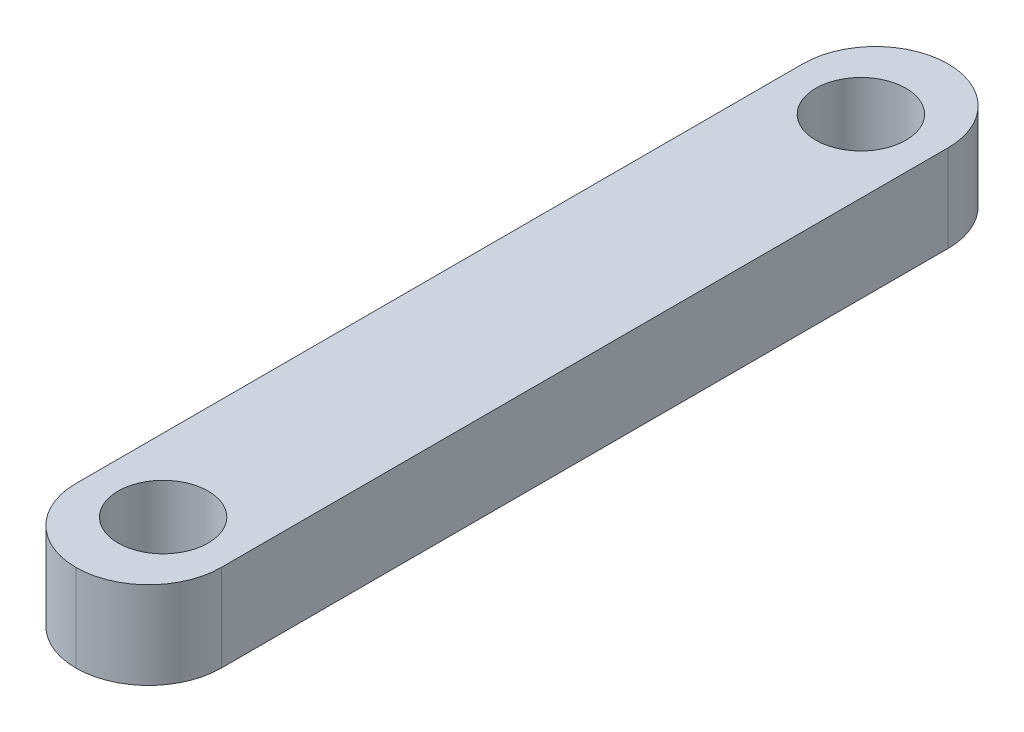
SolidWorks part; units mm, degrees
ref_plane "Front Plane" through (0, 0, 0) normal (0, 0, 1) x (1, 0, 0)
ref_plane "Top Plane" through (0, 0, 0) normal (0, 1, 0) x (1, 0, 0)
ref_plane "Right Plane" through (0, 0, 0) normal (1, 0, 0) x (0, 0, -1)
sketch "Sketch1" plane through (0, 0, 0) normal (0, 1, 0) x (1, 0, 0)
  line L1 (-2.5, -15) -> (2.5, -15)
  line L2 (-2.5, -15) -> (-2.5, 15)
  line L3 (-2.5, 15) -> (2.5, 15)
  line L4 (2.5, -15) -> (2.5, 15)
  line L5 (-2.5, -15) -> (2.5, 15) construction
  line L6 (-2.5, 15) -> (2.5, -15) construction
  circle A0 centre (0, 12) radius 1.55
  circle A1 centre (0, -12) radius 1.55
  point P0 (0, 0)
  dimension "D3" = 3.1
  dimension "D4" = 3.1
  dimension "D1" = 5
  dimension "D2" = 30
  dimension "D5" = 3
  dimension "D6" = 3
  dimension "D7" = 2.5
  dimension "D8" = 2.5
extrude "Boss-Extrude1" add sketch "Sketch1" along normal blind 3
fillet "Fillet1" radius 2.5 4 edges at (-2.5, 1.5, 15) (-2.5, 1.5, -15) (2.5, 1.5, -15) (2.5, 1.5, 15)
